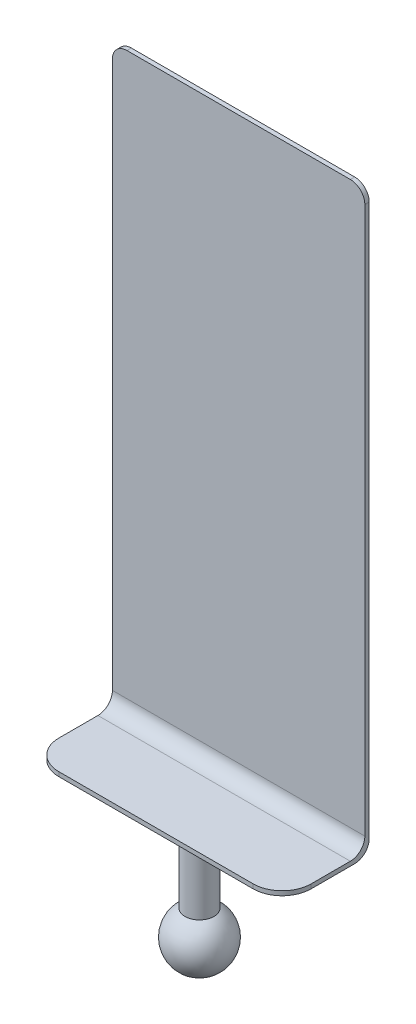
SolidWorks part; units mm, degrees
ref_plane "Front Plane" through (0, 0, 0) normal (0, 0, 1) x (1, 0, 0)
ref_plane "Top Plane" through (0, 0, 0) normal (0, 1, 0) x (1, 0, 0)
ref_plane "Right Plane" through (0, 0, 0) normal (1, 0, 0) x (0, 0, -1)
sketch "Sketch1" plane through (0, 0, 0) normal (0, 1, 0) x (1, 0, 0)
  line L1 (43.5, -0.75) -> (-43.5, -0.75)
  line L2 (43.5, -0.75) -> (43.5, 0.75)
  line L3 (43.5, 0.75) -> (-43.5, 0.75)
  line L4 (-43.5, -0.75) -> (-43.5, 0.75)
  line L5 (43.5, -0.75) -> (-43.5, 0.75) construction
  line L6 (43.5, 0.75) -> (-43.5, -0.75) construction
  point P0 (0, 0)
  dimension "D1" = 87
  dimension "D2" = 1.5
extrude "Boss-Extrude1" add sketch "Sketch1" along normal blind 200
sketch "Sketch2" plane through (0, 0, 0.75) normal (0, 0, 1) x (1, 0, 0)
  line L0 (43.5, 200) -> (43.5, 0) construction
  line L1 (-43.5, 0) -> (43.5, 0)
  line L2 (-43.5, 0) -> (-43.5, 1.5)
  line L3 (-43.5, 1.5) -> (43.5, 1.5)
  line L4 (43.5, 0) -> (43.5, 1.5)
  dimension "D1" = 1.5
extrude "Boss-Extrude2" add sketch "Sketch2" along normal blind 28.5
fillet "Fillet1" radius 5 2 edges at (0, 0, -0.75) (0, 1.5, 0.75)
ref_plane "Plane1" through (0, 0, 14.25) normal (0, 0, 1) x (1, 0, 0)
sketch "Sketch4" plane through (0, 0, 14.25) normal (0, 0, 1) x (1, 0, 0)
  line L0 (5, 0) -> (5, -30)
  line L1 (-43.5, 0) -> (43.5, 0) construction
  line L2 (0, 0) -> (0, -2.8752) construction
  line L3 (0, -2.8752) -> (0, -48.6603) construction
  line L4 (0, 0) -> (0, 0.5918)
  line L5 (0, 0) -> (0, -48.6603)
  line L6 (0, 0.5918) -> (5, 0.5918)
  line L7 (5, 0.5918) -> (5, 0)
  arc A0 (5, -30) -> (0, -48.6603) centre (0, -38.6603) cw
  dimension "D2" = 10
  dimension "D1" = 5
  dimension "D3" = 30
revolve "Revolve1" add sketch "Sketch4" angle 360 about L5
fillet "Fillet2" radius 5 1 edges at (0, 0, 19.25)
fillet "Fillet3" radius 5 2 edges at (43.5, 200, 0) (-43.5, 200, 0)
fillet "Fillet4" radius 10 2 edges at (43.5, 0.75, 29.25) (-43.5, 0.75, 29.25)
